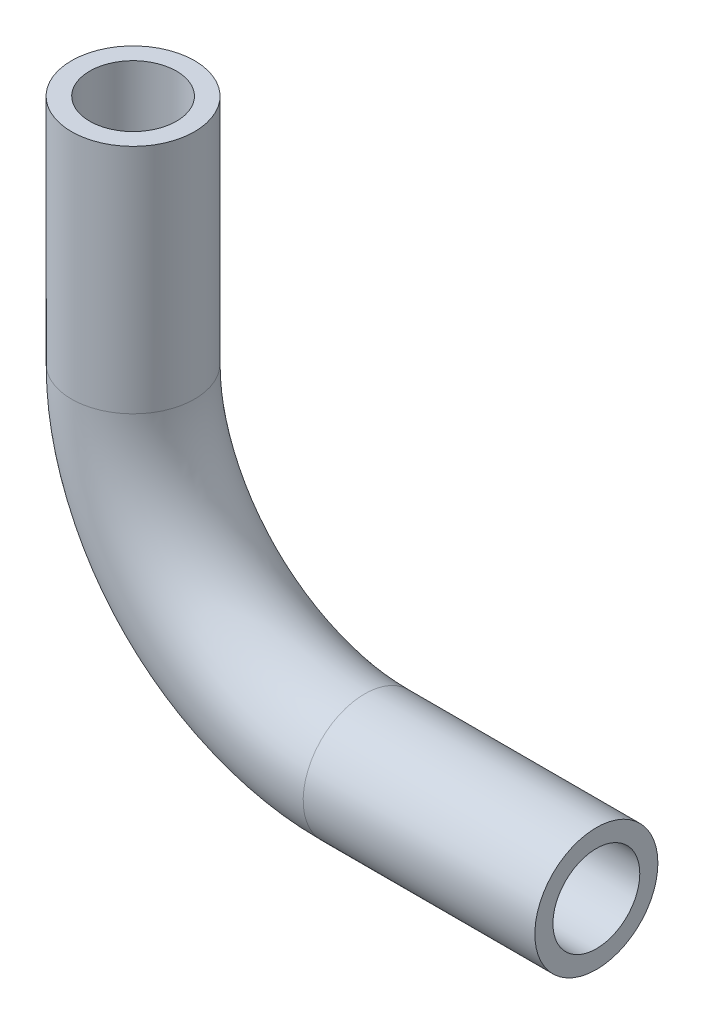
SolidWorks part; units mm, degrees
material "Silicon Rubber"
ref_plane "X-Y Datum" through (0, 0, 0) normal (0, 0, 1) x (1, 0, 0)
ref_plane "X-Z Datum" through (0, 0, 0) normal (0, 1, 0) x (1, 0, 0)
ref_plane "Y-Z Datum" through (0, 0, 0) normal (1, 0, 0) x (0, 0, -1)
sketch "Sketch1" plane through (0, 0, 0) normal (0, 0, 1) x (1, 0, 0)
  line L0 (-50.8, 0) -> (-50.8, -50.8) construction
  line L1 (-50.8, -50.8) -> (0, -50.8) construction
  line L2 (-50.8, 0) -> (-50.8, 50.8)
  line L3 (0, 0) -> (-50.8, 0) construction
  line L4 (0, 0) -> (0, -50.8) construction
  line L5 (0, -50.8) -> (50.8, -50.8)
  arc A0 (0, -50.8) -> (-50.8, 0) centre (0, 0) cw
  dimension "D5" = 50.8
  dimension "D1" = 50.8
  dimension "D2" = 50.8
sweep "Sweep1" add path "Sketch1" circular profile diameter 26.9875 parameters "D3"=26.9875
sweep "Cut-Sweep1" cut path "Sketch1<4>" circular profile diameter 19.05 parameters "D3"=19.05
sketch "Sketch1<4>" plane through (0, 0, 0) normal (0, 0, 1) x (1, 0, 0) same geometry as "Sketch1"
